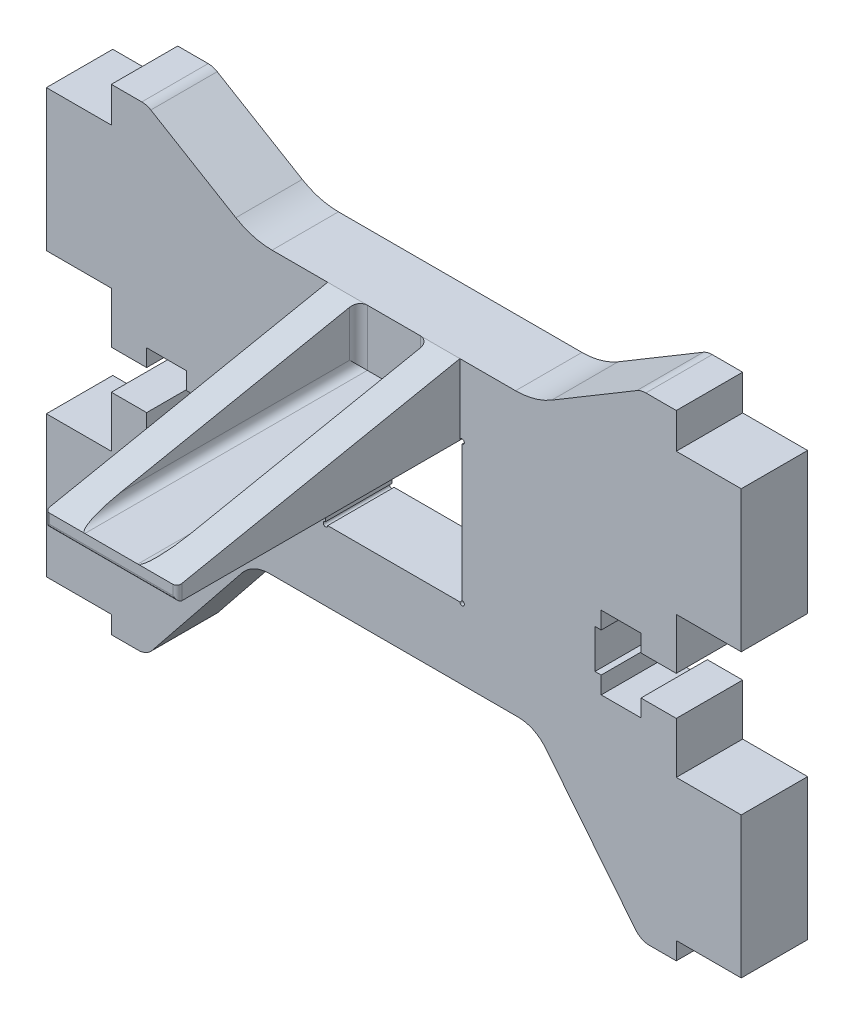
SolidWorks part; units mm, degrees
ref_plane "Front Plane" through (0, 0, 0) normal (0, 0, 1) x (1, 0, 0)
ref_plane "Top Plane" through (0, 0, 0) normal (0, 1, 0) x (1, 0, 0)
ref_plane "Right Plane" through (0, 0, 0) normal (1, 0, 0) x (0, 0, -1)
sketch "Sketch1" plane through (0, 0, 0) normal (0, 0, 1) x (1, 0, 0)
  line L0 (0, 0) -> (0, -22.937) construction
  line L1 (6.1452, -6.3) -> (-6.1452, -6.3)
  line L2 (6.1452, -6.3) -> (6.1452, 6.3)
  line L3 (6.1452, 6.3) -> (-6.1452, 6.3)
  line L4 (-6.1452, -6.3) -> (-6.1452, 6.3)
  line L5 (6.1452, -6.3) -> (-6.1452, 6.3) construction
  line L6 (6.1452, 6.3) -> (-6.1452, -6.3) construction
  line L7 (25.4, -22.937) -> (-25.4, -22.937) construction
  line L8 (25.4, 2.463) -> (25.4, -10.237)
  line L9 (25.4, -22.937) -> (31.242, -22.937)
  line L10 (-31.242, 2.463) -> (-25.4, 2.463)
  line L11 (31.242, -10.237) -> (25.4, -10.237)
  line L12 (31.242, -22.937) -> (31.242, -10.237)
  line L13 (25.4, -22.937) -> (25.4, -24.5245)
  line L14 (-12.7, -12.65) -> (12.7, -12.65)
  line L15 (12.7, -12.65) -> (22.225, -24.5245)
  line L16 (22.225, -24.5245) -> (25.4, -24.5245)
  line L17 (-12.7, 12.65) -> (12.7, 12.65)
  line L18 (-12.7, 12.65) -> (-22.225, 18.338)
  line L19 (-31.242, -10.237) -> (-25.4, -10.237)
  line L20 (-31.242, -22.937) -> (-31.242, -10.237)
  line L21 (-25.4, -22.937) -> (-31.242, -22.937)
  line L22 (-25.4, -22.937) -> (-25.4, -24.5245)
  line L23 (-22.225, -24.5245) -> (-25.4, -24.5245)
  line L24 (-12.7, -12.65) -> (-22.225, -24.5245)
  line L25 (-25.4, 18.338) -> (-22.225, 18.338)
  line L26 (-25.4, 2.463) -> (-25.4, -10.237)
  line L27 (31.242, 2.463) -> (25.4, 2.463)
  line L28 (31.242, 2.463) -> (31.242, 15.163)
  line L29 (31.242, 15.163) -> (25.4, 15.163)
  line L30 (25.4, 15.163) -> (25.4, 18.338)
  line L31 (25.4, 18.338) -> (22.225, 18.338)
  line L32 (-25.4, 15.163) -> (-25.4, 18.338)
  line L33 (12.7, 12.65) -> (22.225, 18.338)
  line L34 (-31.242, 15.163) -> (-25.4, 15.163)
  line L35 (-31.242, 2.463) -> (-31.242, 15.163)
  point P0 (0, 0)
  point P11 (0, -22.937)
  point P28 (0, -12.65)
  point P29 (0, 12.65)
  dimension "D1" = 12.6
  dimension "D2" = 12.2904
  dimension "D3" = 16.637
  dimension "D4" = 50.8
  dimension "D5" = 12.7
  dimension "D6" = 5.842
  dimension "D7" = 12.7
  dimension "D8" = 1.5875
  dimension "D9" = 12.7
  dimension "D10" = 6.35
  dimension "D11" = 3.175
  dimension "D12" = 6.35
  dimension "D13" = 12.7
  dimension "D16" = 12.7
  dimension "D17" = 3.175
  dimension "D18" = 3.175
extrude "Boss-Extrude1" add sketch "Sketch1" along normal blind 5.969
sketch "Sketch2" plane through (0, 0, 5.969) normal (0, 0, 1) x (1, 0, 0)
  line L0 (-25.4, -3.887) -> (25.4, -3.887) construction
  line L1 (-25.4, 2.463) -> (-25.4, -10.237) construction
  line L2 (25.4, -10.237) -> (25.4, 2.463) construction
  line L3 (22.225, -2.1344) -> (22.225, -0.589)
  line L4 (22.225, -5.6396) -> (25.4, -5.6396)
  line L5 (0, -3.887) -> (0, -12.65) construction
  line L6 (22.225, -2.1344) -> (25.4, -2.1344)
  line L7 (25.4, -5.6396) -> (25.4, -2.1344)
  line L8 (22.225, -5.6396) -> (25.4, -2.1344) construction
  line L9 (22.225, -2.1344) -> (25.4, -5.6396) construction
  line L10 (18.65, -7.185) -> (22.225, -7.185)
  line L11 (18.65, -7.185) -> (18.65, -5.6396)
  line L12 (18.65, -0.589) -> (22.225, -0.589)
  line L13 (22.225, -7.185) -> (22.225, -5.6396)
  line L14 (18.65, -7.185) -> (22.225, -0.589) construction
  line L15 (18.65, -0.589) -> (22.225, -7.185) construction
  line L16 (18.092, -5.6396) -> (18.65, -5.6396)
  line L17 (18.092, -5.6396) -> (18.092, -2.1344)
  line L18 (18.092, -2.1344) -> (18.65, -2.1344)
  line L19 (-12.7, -12.65) -> (12.7, -12.65) construction
  line L20 (18.092, -5.6396) -> (18.65, -2.1344) construction
  line L21 (18.092, -2.1344) -> (18.65, -5.6396) construction
  line L22 (18.65, -2.1344) -> (18.65, -0.589)
  line L23 (-18.092, -2.1344) -> (-18.65, -5.6396) construction
  line L24 (-18.092, -5.6396) -> (-18.65, -2.1344) construction
  line L25 (-18.65, -0.589) -> (-22.225, -7.185) construction
  line L26 (-18.65, -7.185) -> (-22.225, -0.589) construction
  line L27 (-22.225, -2.1344) -> (-25.4, -5.6396) construction
  line L28 (-22.225, -5.6396) -> (-25.4, -2.1344) construction
  line L29 (-18.65, -2.1344) -> (-18.65, -0.589)
  line L30 (-18.092, -2.1344) -> (-18.65, -2.1344)
  line L31 (-18.092, -5.6396) -> (-18.092, -2.1344)
  line L32 (-18.092, -5.6396) -> (-18.65, -5.6396)
  line L33 (-22.225, -7.185) -> (-22.225, -5.6396)
  line L34 (-18.65, -0.589) -> (-22.225, -0.589)
  line L35 (-18.65, -7.185) -> (-18.65, -5.6396)
  line L36 (-18.65, -7.185) -> (-22.225, -7.185)
  line L37 (-25.4, -5.6396) -> (-25.4, -2.1344)
  line L38 (-22.225, -2.1344) -> (-25.4, -2.1344)
  line L39 (-22.225, -5.6396) -> (-25.4, -5.6396)
  line L40 (-22.225, -2.1344) -> (-22.225, -0.589)
  point P6 (23.8125, -3.887)
  point P11 (20.4375, -3.887)
  point P16 (18.371, -3.887)
  point P37 (-18.371, -3.887)
  point P38 (-20.4375, -3.887)
  point P39 (-23.8125, -3.887)
  dimension "D1" = 3.175
  dimension "D2" = 3.575
  dimension "D3" = 3.5052
  dimension "D4" = 6.596
  dimension "D5" = 0.558
extrude "Cut-Extrude1" cut sketch "Sketch2" against normal through all
sketch "Sketch3" plane through (0, 0, 5.969) normal (0, 0, 1) x (1, 0, 0)
  line L0 (-6.1452, 0) -> (6.1452, 0) construction
  line L1 (-6.1452, 6.3) -> (-6.1452, -6.3) construction
  line L2 (6.1452, -6.3) -> (6.1452, 6.3) construction
  circle A0 centre (6.1452, 6.3) radius 0.1984
  circle A1 centre (-6.1452, 6.3) radius 0.1984
  circle A2 centre (-6.1452, -6.3) radius 0.1984
  circle A3 centre (6.1452, -6.3) radius 0.1984
  dimension "D1" = 0.3969
  dimension "D2" = 0.3969
extrude "Cut-Extrude2" cut sketch "Sketch3" against normal through all
fillet "Fillet1" radius 3.175 2 edges at (-12.7, -12.65, 2.9845) (12.7, -12.65, 2.9845)
fillet "Fillet2" radius 1.5875 4 edges at (22.225, -24.5245, 2.9845) (-22.225, -24.5245, 2.9845) (-22.225, 18.338, 2.9845) (22.225, 18.338, 2.9845)
sketch "Sketch4" plane through (0, 0, 5.969) normal (0, 0, 1) x (1, 0, 0)
  line L0 (-6.1452, 0) -> (6.1452, 0) construction
  line L1 (-6.1452, 6.1016) -> (-6.1452, -6.1016) construction
  line L2 (6.1452, -6.1016) -> (6.1452, 6.1016) construction
  line L4 (6.35, -5.5562) -> (-6.35, -5.5563)
  line L5 (6.35, -5.5562) -> (6.35, 5.5563)
  line L6 (6.35, 5.5563) -> (-6.35, 5.5562)
  line L7 (-6.35, -5.5563) -> (-6.35, 5.5562)
  line L8 (6.35, -5.5562) -> (-6.35, 5.5562) construction
  line L9 (6.35, 5.5563) -> (-6.35, -5.5563) construction
  point P6 (0, 0)
  dimension "D1" = 12.7
  dimension "D2" = 11.1125
extrude "Cut-Extrude3" [suppressed] cut sketch "Sketch4" against normal through all
fillet "Fillet7" [suppressed] radius 0.1
sketch "Sketch5" plane through (0, 0, 5.969) normal (0, 0, 1) x (1, 0, 0)
  line L0 (5.9468, 6.3) -> (-5.9468, 6.3) construction
  line L1 (5.08, 6.05) -> (-5.08, 6.05)
  line L2 (5.08, 6.05) -> (5.08, 6.55)
  line L3 (5.08, 6.55) -> (-5.08, 6.55)
  line L4 (-5.08, 6.05) -> (-5.08, 6.55)
  line L5 (5.08, 6.05) -> (-5.08, 6.55) construction
  line L6 (5.08, 6.55) -> (-5.08, 6.05) construction
  point P0 (0, 6.3)
  dimension "D1" = 10.16
  dimension "D2" = 0.5
extrude "Cut-Extrude4" [suppressed] cut sketch "Sketch5" against normal through all
fillet "Fillet8" [suppressed] radius 0.1
sketch "Sketch6" plane through (0, 0, 5.969) normal (0, 0, 1) x (1, 0, 0)
  line L0 (-12.7, 12.65) -> (-12.7, -12.65) construction
  line L1 (12.7, 12.65) -> (-12.7, 12.65) construction
  line L2 (-11.1766, -12.65) -> (11.1766, -12.65) construction
  line L3 (-15.7, 6.3) -> (-9.7, 6.3) construction
  line L4 (-15.7, 7.3) -> (-9.7, 7.3)
  line L5 (-15.7, 5.3) -> (-9.7, 5.3)
  line L6 (-15.7, -0.05) -> (-9.7, -0.05) construction
  line L7 (-15.7, 0.95) -> (-9.7, 0.95)
  line L8 (-15.7, -1.05) -> (-9.7, -1.05)
  arc A0 (-15.7, 7.3) -> (-15.7, 5.3) centre (-15.7, 6.3) ccw
  arc A1 (-9.7, 5.3) -> (-9.7, 7.3) centre (-9.7, 6.3) ccw
  arc A2 (-15.7, 0.95) -> (-15.7, -1.05) centre (-15.7, -0.05) ccw
  arc A3 (-9.7, -1.05) -> (-9.7, 0.95) centre (-9.7, -0.05) ccw
  point P8 (-12.7, 6.3)
  point P17 (-12.7, -0.05)
  point P18 (-12.7, -2.413)
  dimension "D2" = 1
  dimension "D1" = 6
  dimension "D3" = 12.7
  dimension "D5" = 6.35
extrude "Cut-Extrude5" [suppressed] cut sketch "Sketch6" against normal through all
fillet "Fillet9" radius 6.35 2 edges at (12.7, 12.65, 2.9845) (-12.7, 12.65, 2.9845)
sketch "Sketch7" plane through (0, 0, 5.969) normal (0, 0, 1) x (1, 0, 0)
  line L0 (0, 12.65) -> (0, -12.65) construction
  line L1 (10.9483, 12.65) -> (-10.9483, 12.65) construction
  line L2 (-11.1766, -12.65) -> (11.1766, -12.65) construction
  line L4 (6.35, 9.475) -> (-6.35, 9.475)
  line L5 (6.35, 9.475) -> (6.35, 12.65)
  line L6 (6.35, 12.65) -> (-6.35, 12.65)
  line L7 (-6.35, 9.475) -> (-6.35, 12.65)
  line L8 (6.35, 9.475) -> (-6.35, 12.65) construction
  line L9 (6.35, 12.65) -> (-6.35, 9.475) construction
  point P6 (0, 11.0625)
  dimension "D1" = 12.7
  dimension "D2" = 3.175
extrude "Boss-Extrude2" [suppressed] add sketch "Sketch7" along normal blind 3.175
sketch "Sketch8" [suppressed] plane through (-6.35, 0, 0) normal (-1, 0, 0) x (0, 0, 1)
  line L0 (5.969, 9.475) -> (5.969, 6.681)
  line L1 (5.969, 6.681) -> (9.144, 9.475)
  line L2 (9.144, 9.475) -> (5.969, 9.475) construction
  line L3 (9.144, 9.475) -> (5.969, 9.475)
  dimension "D1" = 2.794
extrude "Boss-Extrude3" [suppressed] add sketch "Sketch8" against normal blind 3.175
sketch "Sketch9" [suppressed] plane through (0, 0, 9.144) normal (0, 0, 1) x (1, 0, 0)
  line L0 (0, 12.65) -> (0, 9.475) construction
  line L1 (6.35, 12.65) -> (-6.35, 12.65) construction
  line L2 (-3.175, 9.475) -> (6.35, 9.475) construction
ref_plane "Plane1" [suppressed] through (0, 0, 0) normal (1, 0, 0) x (0, 0, -1)
mirror "Mirror1" [suppressed] about plane through (0, 0, 0) normal (1, 0, 0)
chamfer "Chamfer1" [suppressed] distance 1.27 angle 45
sketch "Sketch10" [suppressed] plane through (0, 0, 5.969) normal (0, 0, 1) x (1, 0, 0)
  line L0 (0, 12.65) -> (0, -12.65) construction
  line L1 (10.9483, 12.65) -> (7.62, 12.65) construction
  line L2 (-11.1766, -12.65) -> (11.1766, -12.65) construction
  line L3 (5.9468, 6.3) -> (-5.9468, 6.3) construction
  line L4 (6.35, 9.475) -> (-6.35, 9.475)
  line L5 (6.35, 9.475) -> (6.35, 6.3)
  line L6 (6.35, 6.3) -> (-6.35, 6.3)
  line L7 (-6.35, 9.475) -> (-6.35, 6.3)
  line L8 (6.35, 9.475) -> (-6.35, 6.3) construction
  line L9 (6.35, 6.3) -> (-6.35, 9.475) construction
  point P6 (0, 7.8875)
  dimension "D1" = 3.175
  dimension "D2" = 12.7
extrude "Boss-Extrude4" [suppressed] add sketch "Sketch10" along normal blind 25.4
sketch "Sketch12" [suppressed] plane through (0, 0, 31.369) normal (0, 0, 1) x (1, 0, 0)
  line L0 (-6.35, 6.3) -> (-7.9726, 12.65)
  line L1 (10.9483, 12.65) -> (-10.9483, 12.65) construction
  line L2 (-7.9726, 12.65) -> (-7.1613, 12.65)
  line L3 (-7.1613, 12.65) -> (-6.35, 9.475)
  line L4 (-6.35, 9.475) -> (-6.35, 6.3)
  line L5 (0, 9.475) -> (0, 6.3) construction
  line L6 (6.35, 9.475) -> (-6.35, 9.475) construction
  line L7 (-6.35, 6.3) -> (6.35, 6.3) construction
  line L8 (6.35, 9.475) -> (6.35, 6.3)
  line L9 (7.1613, 12.65) -> (6.35, 9.475)
  line L10 (7.9726, 12.65) -> (7.1613, 12.65)
  line L11 (6.35, 6.3) -> (7.9726, 12.65)
extrude "Boss-Extrude5" [suppressed] add sketch "Sketch12" against normal up to surface (25.4 mm away) up to face at (0, 0, 5.969)
chamfer "Chamfer2" [suppressed] distance 3.175 angle 45
fillet "Fillet10" [suppressed] radius 2.54
sketch "Sketch13" plane through (0, 0, 5.969) normal (0, 0, 1) x (1, 0, 0)
  line L0 (0, 6.3) -> (0, 12.65) construction
  line L1 (5.9468, 6.3) -> (-5.9468, 6.3) construction
  line L2 (10.9483, 12.65) -> (-10.9483, 12.65) construction
  line L4 (5.9468, 12.65) -> (-5.9468, 12.65)
  line L5 (5.9468, 12.65) -> (5.9468, 6.3)
  line L6 (5.9468, 6.3) -> (-5.9468, 6.3)
  line L7 (-5.9468, 12.65) -> (-5.9468, 6.3)
  line L8 (5.9468, 12.65) -> (-5.9468, 6.3) construction
  line L9 (5.9468, 6.3) -> (-5.9468, 12.65) construction
  point P6 (0, 9.475)
extrude "Boss-Extrude6" add sketch "Sketch13" along normal blind 25.4
sketch "Sketch14" plane through (-5.9468, 0, 0) normal (-1, 0, 0) x (0, 0, 1)
  line L0 (5.969, 12.65) -> (31.369, 7.57)
  line L1 (31.369, 12.65) -> (31.369, 6.3) construction
  line L2 (31.369, 7.57) -> (31.369, 12.65)
  line L3 (31.369, 12.65) -> (5.969, 12.65) construction
  line L4 (31.369, 12.65) -> (5.969, 12.65)
  dimension "D1" = 5.08
extrude "Cut-Extrude6" cut sketch "Sketch14" against normal through all
sketch "Sketch15" plane through (0, 0, 31.369) normal (0, 0, 1) x (1, 0, 0)
  line L0 (0, 7.57) -> (0, 12.65) construction
  line L1 (5.9468, 7.57) -> (-5.9468, 7.57) construction
  line L2 (5.9468, 12.65) -> (-5.9468, 12.65) construction
  line L4 (3.175, 12.65) -> (-3.175, 12.65)
  line L5 (3.175, 12.65) -> (3.175, 7.57)
  line L6 (3.175, 7.57) -> (-3.175, 7.57)
  line L7 (-3.175, 12.65) -> (-3.175, 7.57)
  line L8 (3.175, 12.65) -> (-3.175, 7.57) construction
  line L9 (3.175, 7.57) -> (-3.175, 12.65) construction
  point P6 (0, 10.11)
  dimension "D1" = 6.35
extrude "Cut-Extrude7" cut sketch "Sketch15" against normal up to surface (25.4 mm away) up to face at (0, -2.3884, 5.969)
fillet "Fillet13" radius 0.7937 4 edges at (-3.175, 7.57, 18.669) (3.175, 7.57, 18.669) (-3.175, 10.11, 5.969) (3.175, 10.11, 5.969)
fillet "Fillet14" radius 0.3969 3 edges at (0, 6.3, 31.369) (5.9468, 6.935, 31.369) (-5.9468, 6.935, 31.369)
